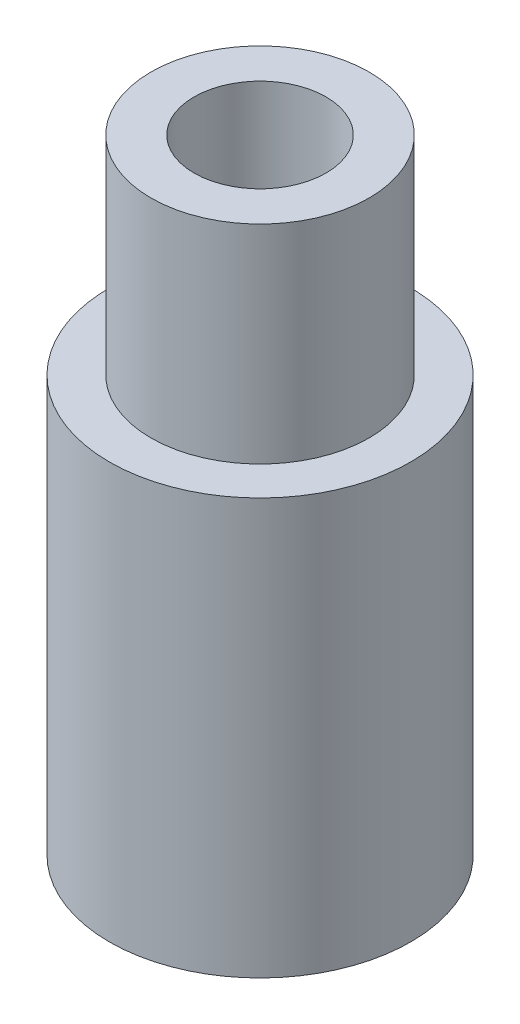
SolidWorks part; units mm, degrees
ref_plane "Front Plane" through (0, 0, 0) normal (0, 0, 1) x (1, 0, 0)
ref_plane "Top Plane" through (0, 0, 0) normal (0, 1, 0) x (1, 0, 0)
ref_plane "Right Plane" through (0, 0, 0) normal (1, 0, 0) x (0, 0, -1)
sketch "Sketch1" plane through (0, 0, 0) normal (0, 1, 0) x (1, 0, 0)
  circle A0 centre (0, 0) radius 3.175
  circle A1 centre (0, 0) radius 7.25
  dimension "D1" = 6.35
  dimension "D2" = 14.5
extrude "Boss-Extrude1" add sketch "Sketch1" along normal blind 30
sketch "Sketch2" plane through (0, 30, 0) normal (0, 1, 0) x (1, 0, 0)
  circle A0 centre (0, 0) radius 5.25
  dimension "D1" = 10.5
extrude "Cut-Extrude1" cut sketch "Sketch2" against normal blind 10 flip side to cut
sketch "Sketch3" plane through (0, 0, 0) normal (0, -1, 0) x (1, 0, 0)
  circle A1 centre (0, 0) radius 4.25
  dimension "D1" = 8.5
extrude "Cut-Extrude2" cut sketch "Sketch3" against normal blind 9
